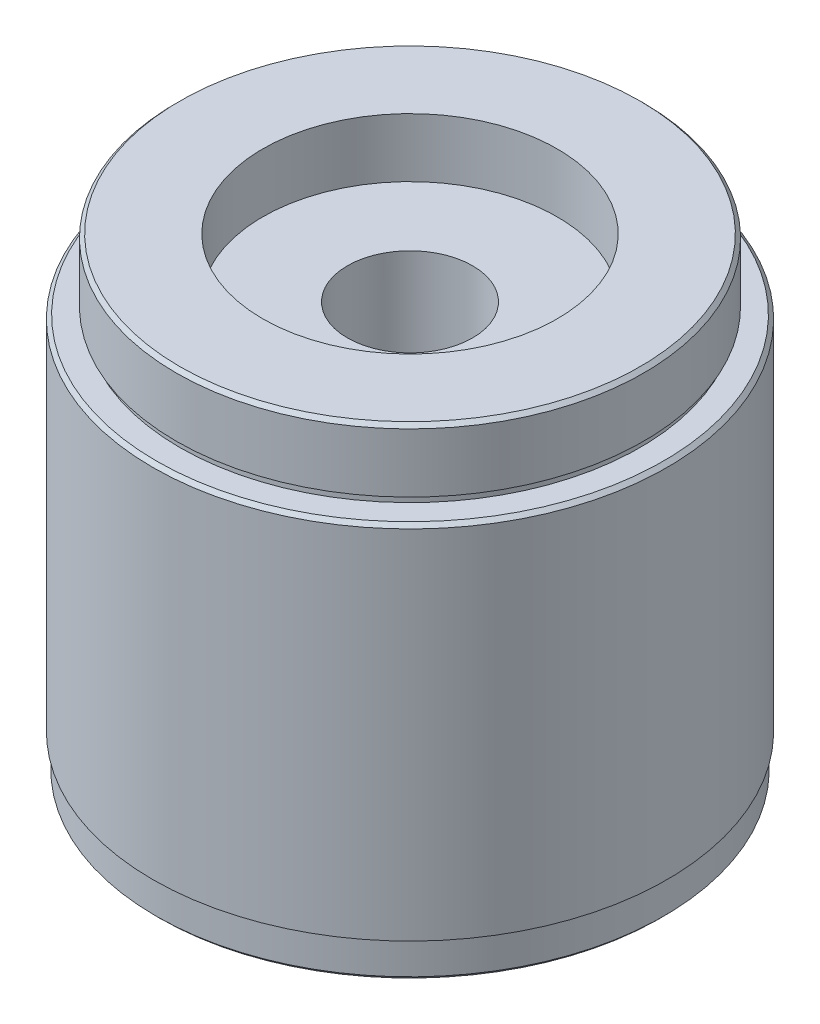
SolidWorks part; units mm, degrees
ref_plane "Front Plane" through (0, 0, 0) normal (0, 0, 1) x (1, 0, 0)
ref_plane "Top Plane" through (0, 0, 0) normal (0, 1, 0) x (1, 0, 0)
ref_plane "Right Plane" through (0, 0, 0) normal (1, 0, 0) x (0, 0, -1)
sketch "Sketch1" plane through (0, 0, 0) normal (0, 1, 0) x (1, 0, 0)
  circle A0 centre (0, 0) radius 34.925
extrude "Boss-Extrude1" add sketch "Sketch1" along normal blind 63.5 separate body
sketch "Sketch2" plane through (0, 0, 0) normal (0, -1, 0) x (1, 0, 0)
  circle A0 centre (0, 0) radius 34.5
extrude "Cut-Extrude1" cut sketch "Sketch2" against normal blind 5 flip side to cut
sketch "Sketch3" plane through (0, 63.5, 0) normal (0, 1, 0) x (1, 0, 0)
  circle A0 centre (0, 0) radius 31.75
extrude "Cut-Extrude2" cut sketch "Sketch3" against normal blind 9.52 flip side to cut
sketch "Sketch4" plane through (0, 53.98, 0) normal (0, 1, 0) x (1, 0, 0)
  circle A0 centre (0, 0) radius 31.25
extrude "Cut-Extrude3" cut sketch "Sketch4" along normal blind 1 flip side to cut
sketch "Sketch5" plane through (0, 63.5, 0) normal (0, 1, 0) x (1, 0, 0)
  circle A0 centre (0, 0) radius 20
extrude "Cut-Extrude4" cut sketch "Sketch5" against normal blind 8
sketch "Sketch6" plane through (0, 0, 0) normal (0, -1, 0) x (1, 0, 0)
  circle A0 centre (0, 0) radius 8.5
extrude "Cut-Extrude5" cut sketch "Sketch6" against normal through all
sketch "Sketch7" plane through (0, 0, 0) normal (0, -1, 0) x (1, 0, 0)
  circle A0 centre (0, 0) radius 14.5
extrude "Cut-Extrude6" cut sketch "Sketch7" against normal blind 5
chamfer "Chamfer1" distance 0.5 angle 45 1 edges at (0, 0, -34.5) first distance on face at (0, 0, -14.5)
chamfer "Chamfer2" distance 0.5 angle 45 1 edges at (0, 63.5, 31.75) first distance on face at (0, 63.5, 20)
chamfer "Chamfer3" distance 0.5 angle 45 1 edges at (0, 53.98, 34.925) first distance on face at (0, 53.98, 34.925)
